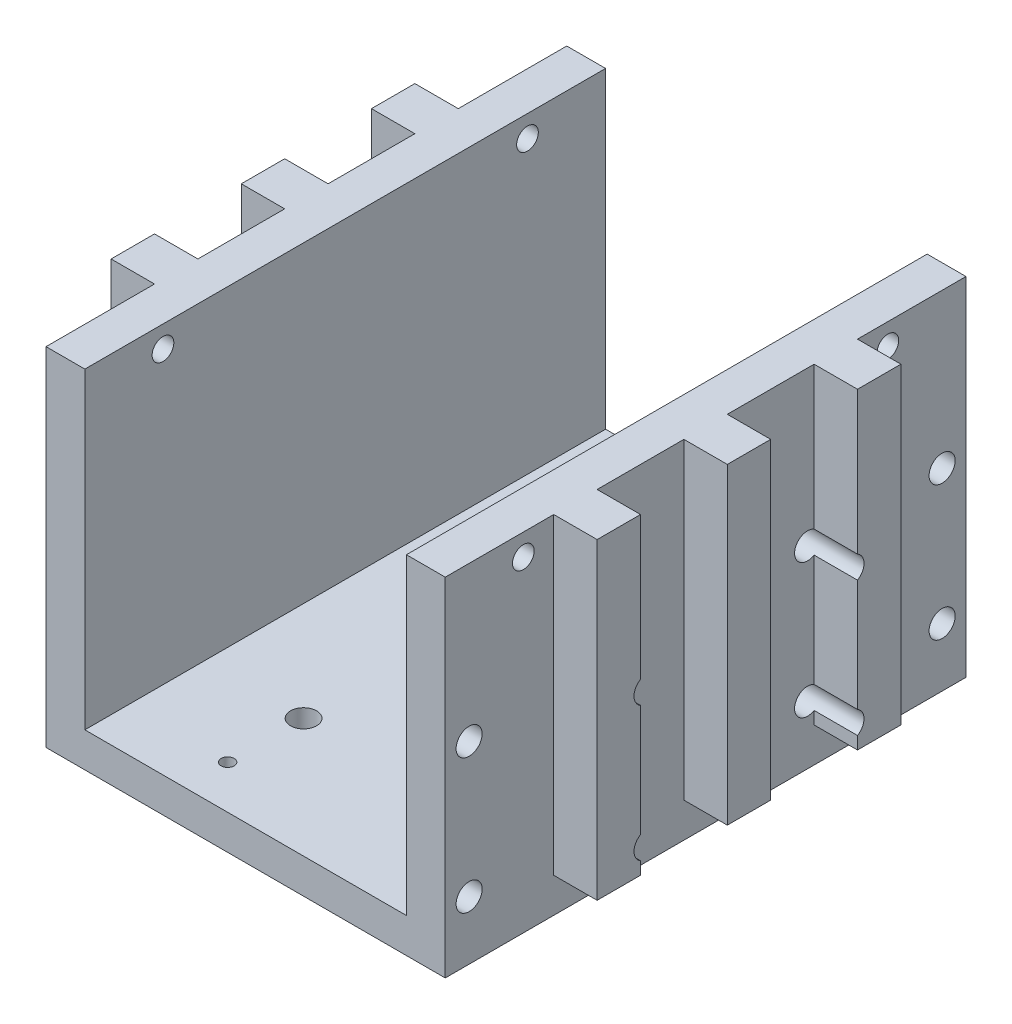
SolidWorks part; units mm, degrees
material "1060 Alloy"
ref_plane "Front Plane" through (0, 0, 0) normal (0, 0, 1) x (1, 0, 0)
ref_plane "Top Plane" through (0, 0, 0) normal (0, 1, 0) x (1, 0, 0)
ref_plane "Right Plane" through (0, 0, 0) normal (1, 0, 0) x (0, 0, -1)
sketch "Sketch1" plane through (0, 0, 0) normal (0, 1, 0) x (1, 0, 0)
  line L1 (0, 0) -> (92, 0)
  line L2 (0, 0) -> (0, 120)
  line L3 (0, 120) -> (92, 120)
  line L4 (92, 0) -> (92, 120)
  dimension "D1" = 120
  dimension "D2" = 92
extrude "Boss-Extrude1" add sketch "Sketch1" along normal blind 8
sketch "Sketch2" plane through (0, 8, 0) normal (0, 1, 0) x (1, 0, 0)
  line L0 (0, 120) -> (8.9486, 120)
  line L1 (92, 120) -> (0, 120) construction
  line L2 (8.9486, 120) -> (8.9486, 0)
  line L3 (0, 0) -> (92, 0) construction
  line L4 (8.9486, 0) -> (0, 0)
  line L5 (0, 0) -> (0, 25)
  line L6 (0, 120) -> (0, 0) construction
  line L7 (0, 25) -> (-10, 25)
  line L8 (-10, 25) -> (-10, 35)
  line L9 (-10, 35) -> (0, 35)
  line L12 (-10, 55) -> (-10, 65)
  line L13 (-10, 65) -> (0, 65)
  line L14 (0, 65) -> (0, 85)
  line L15 (0, 85) -> (-10, 85)
  line L16 (-10, 85) -> (-10, 95)
  line L17 (-10, 95) -> (0, 95)
  line L18 (0, 95) -> (0, 120)
  line L19 (-10, 55) -> (0, 55)
  line L20 (0, 55) -> (0, 35)
  line L21 (46, 120) -> (46, 0) construction
  line L22 (92, 55) -> (92, 35)
  line L23 (102, 55) -> (92, 55)
  line L24 (92, 95) -> (92, 120)
  line L25 (102, 95) -> (92, 95)
  line L26 (102, 85) -> (102, 95)
  line L27 (92, 85) -> (102, 85)
  line L28 (92, 65) -> (92, 85)
  line L29 (102, 65) -> (92, 65)
  line L30 (102, 55) -> (102, 65)
  line L31 (102, 35) -> (92, 35)
  line L32 (102, 25) -> (102, 35)
  line L33 (92, 25) -> (102, 25)
  line L34 (92, 0) -> (92, 25)
  line L35 (83.0514, 0) -> (92, 0)
  line L36 (83.0514, 120) -> (83.0514, 0)
  line L37 (92, 120) -> (83.0514, 120)
  line L38 (92, 0) -> (92, 120) construction
  point P42 (92, 92.5)
  dimension "D1" = 25
  dimension "D2" = 10
  dimension "D3" = 10
  dimension "D4" = 20
  dimension "D5" = 10
  dimension "D6" = 20
  dimension "D7" = 25
  dimension "D8" = 10
  dimension "D10" = 10
extrude "Boss-Extrude2" add sketch "Sketch2" along normal blind 72
sketch "Sketch3" plane through (0, 0, 0) normal (0, -1, 0) x (1, 0, 0)
  line L0 (31.85, 0) -> (31.85, -120) construction
  line L1 (0, 0) -> (92, 0) construction
  line L2 (92, -120) -> (0, -120) construction
  line L3 (92, -92.5) -> (0, -92.5) construction
  line L4 (92, 0) -> (92, -120) construction
  line L5 (0, -120) -> (0, 0) construction
  line L6 (0, -60) -> (92, -60) construction
  line L7 (92, -55) -> (92, -65) construction
  circle A0 centre (31.85, -92.5) radius 3
  circle A1 centre (31.85, -110) radius 1.5
  circle A4 centre (31.85, -10) radius 1.5
  circle A5 centre (31.85, -27.5) radius 3
  dimension "D2" = 6
  dimension "D5" = 3
  dimension "D1" = 27.5
  dimension "D3" = 31.85
  dimension "D4" = 17.5
extrude "Cut-Extrude1" cut sketch "Sketch3" against normal up to next
sketch "Sketch4" plane through (83.0514, 0, 0) normal (-1, 0, 0) x (0, 0, 1)
  line L0 (-120, 80) -> (-120, 8) construction
  line L1 (-120, 8) -> (0, 8) construction
  line L2 (0, 80) -> (0, 8) construction
  circle A0 centre (-114.5, 13.5) radius 1.25
  circle A1 centre (-114.5, 44.5) radius 1.25
  circle A2 centre (-83.5, 44.5) radius 1.25
  circle A3 centre (-83.5, 13.5) radius 1.25
  circle A4 centre (-36.5, 44.5) radius 1.25
  circle A5 centre (-5.5, 44.5) radius 1.25
  circle A6 centre (-36.5, 13.5) radius 1.25
  circle A7 centre (-5.5, 13.5) radius 1.25
  dimension "D7" = 2.5
  dimension "D1" = 31
  dimension "D2" = 5.5
  dimension "D3" = 5.5
  dimension "D4" = 31
  dimension "D5" = 31
  dimension "D6" = 5.5
extrude "Cut-Extrude2" cut sketch "Sketch4" against normal up to next
sketch "Sketch5" plane through (102, 0, 0) normal (1, 0, 0) x (0, 0, -1)
  circle A0 centre (5.5, 44.5) radius 3
  circle A1 centre (36.5, 44.5) radius 3
  circle A2 centre (83.5, 44.5) radius 3
  circle A3 centre (114.5, 44.5) radius 3
  circle A4 centre (114.5, 13.5) radius 3
  circle A5 centre (83.5, 13.5) radius 3
  circle A6 centre (36.5, 13.5) radius 3
  circle A7 centre (5.5, 13.5) radius 3
  dimension "D1" = 6
extrude "Cut-Extrude3" cut sketch "Sketch5" against normal blind 15
sketch "Sketch6" plane through (92, 0, 0) normal (1, 0, 0) x (0, 0, -1)
  line L0 (0, 80) -> (0, 0) construction
  line L1 (120, 80) -> (120, 0) construction
  line L2 (0, 80) -> (25, 80) construction
  circle A0 centre (18, 75) radius 2.5
  circle A1 centre (102, 75) radius 2.5
  point P4 (0, 0)
  dimension "D4" = 5
  dimension "D1" = 18
  dimension "D2" = 18
  dimension "D3" = 5
extrude "Cut-Extrude4" cut sketch "Sketch6" against normal through all
